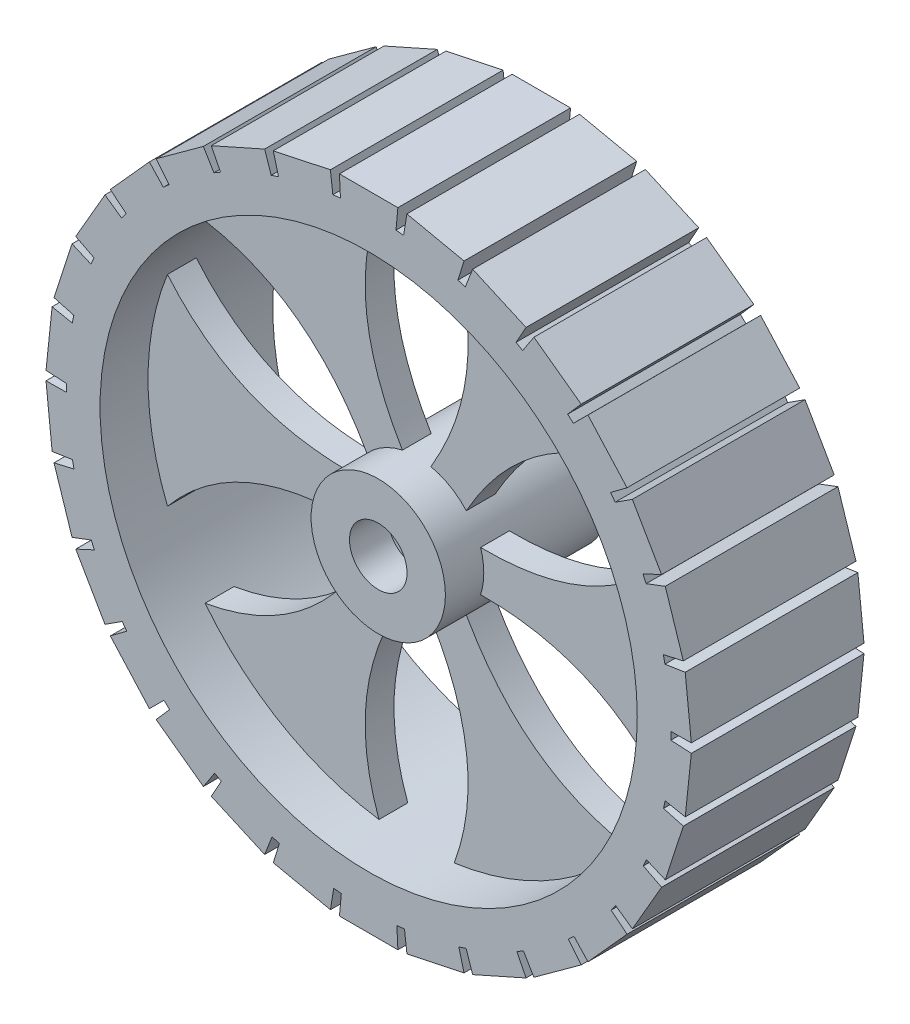
SolidWorks part; units mm, degrees
ref_plane "Front Plane" through (0, 0, 0) normal (0, 0, 1) x (1, 0, 0)
ref_plane "Top Plane" through (0, 0, 0) normal (0, 1, 0) x (1, 0, 0)
ref_plane "Right Plane" through (0, 0, 0) normal (1, 0, 0) x (0, 0, -1)
sketch "Sketch1" plane through (0, 0, 0) normal (0, 0, 1) x (1, 0, 0)
  line L0 (0, 31.5) -> (0, 33.5) construction
  line L1 (-4, 33.5) -> (4, 33.5)
  line L2 (-4, 33.5) -> (-3.7347, 31.2778)
  line L3 (4, 33.5) -> (3.6431, 31.2886)
  line L4 (3.0525, 33.5996) -> (2.85, 31.3708)
  line L5 (10.8776, 31.9363) -> (10.0688, 29.8474)
  line L6 (3.0525, 33.5996) -> (10.8776, 31.9363)
  line L7 (9.9715, 32.2307) -> (9.3101, 30.0927)
  line L8 (17.2799, 28.9768) -> (16.0544, 27.1018)
  line L9 (9.9715, 32.2307) -> (17.2799, 28.9768)
  line L10 (16.4547, 29.4532) -> (15.3632, 27.4995)
  line L11 (22.9269, 24.7509) -> (21.3383, 23.1717)
  line L12 (16.4547, 29.4532) -> (22.9269, 24.7509)
  line L13 (22.2188, 25.3885) -> (20.745, 23.7043)
  line L14 (27.5719, 19.4433) -> (25.6897, 18.2288)
  line L15 (22.2188, 25.3885) -> (27.5719, 19.4433)
  line L16 (27.0119, 20.2141) -> (25.2201, 18.8732)
  line L17 (31.0119, 13.2859) -> (28.9183, 12.4893)
  line L18 (27.0119, 20.2141) -> (31.0119, 13.2859)
  line L19 (30.6243, 14.1563) -> (28.5929, 13.2173)
  line L20 (33.0965, 6.5478) -> (30.883, 6.2039)
  line L21 (30.6243, 14.1563) -> (33.0965, 6.5478)
  line L22 (32.8984, 7.4798) -> (30.7161, 6.9836)
  line L23 (33.7346, -0.4764) -> (31.498, -0.3526)
  line L24 (32.8984, 7.4798) -> (33.7346, -0.4764)
  line L25 (33.7346, 0.4764) -> (31.4969, 0.4448)
  line L26 (32.8984, -7.4798) -> (30.7364, -6.8937)
  line L27 (33.7346, 0.4764) -> (32.8984, -7.4798)
  line L28 (33.0965, -6.5478) -> (30.9011, -6.1135)
  line L29 (30.6243, -14.1563) -> (28.6315, -13.1335)
  line L30 (33.0965, -6.5478) -> (30.6243, -14.1563)
  line L31 (31.0119, -13.2859) -> (28.9547, -12.4046)
  line L32 (27.0119, -20.2141) -> (25.2752, -18.7993)
  line L33 (31.0119, -13.2859) -> (27.0119, -20.2141)
  line L34 (27.5719, -19.4433) -> (25.7429, -18.1536)
  line L35 (22.2188, -25.3885) -> (20.8143, -23.6435)
  line L36 (27.5719, -19.4433) -> (22.2188, -25.3885)
  line L37 (22.9269, -24.7509) -> (21.4061, -23.1091)
  line L38 (16.4547, -29.4532) -> (15.4437, -27.4544)
  line L39 (22.9269, -24.7509) -> (16.4547, -29.4532)
  line L40 (17.2799, -28.9768) -> (16.1336, -27.0547)
  line L41 (9.9715, -32.2307) -> (9.3981, -30.0654)
  line L42 (17.2799, -28.9768) -> (9.9715, -32.2307)
  line L43 (10.8776, -31.9363) -> (10.1561, -29.8178)
  line L44 (3.0525, -33.5996) -> (2.9418, -31.3623)
  line L45 (10.8776, -31.9363) -> (3.0525, -33.5996)
  line L46 (4, -33.5) -> (3.7347, -31.2778)
  line L47 (-4, -33.5) -> (-3.6431, -31.2886)
  line L48 (4, -33.5) -> (-4, -33.5)
  line L49 (-3.0525, -33.5996) -> (-2.85, -31.3708)
  line L50 (-10.8776, -31.9363) -> (-10.0688, -29.8474)
  line L51 (-3.0525, -33.5996) -> (-10.8776, -31.9363)
  line L52 (-9.9715, -32.2307) -> (-9.3101, -30.0927)
  line L53 (-17.2799, -28.9768) -> (-16.0544, -27.1018)
  line L54 (-9.9715, -32.2307) -> (-17.2799, -28.9768)
  line L55 (-16.4547, -29.4532) -> (-15.3632, -27.4995)
  line L56 (-22.9269, -24.7509) -> (-21.3383, -23.1717)
  line L57 (-16.4547, -29.4532) -> (-22.9269, -24.7509)
  line L58 (-22.2188, -25.3885) -> (-20.745, -23.7043)
  line L59 (-27.5719, -19.4433) -> (-25.6897, -18.2288)
  line L60 (-22.2188, -25.3885) -> (-27.5719, -19.4433)
  line L61 (-27.0119, -20.2141) -> (-25.2201, -18.8732)
  line L62 (-31.0119, -13.2859) -> (-28.9183, -12.4893)
  line L63 (-27.0119, -20.2141) -> (-31.0119, -13.2859)
  line L64 (-30.6243, -14.1563) -> (-28.5929, -13.2173)
  line L65 (-33.0965, -6.5478) -> (-30.883, -6.2039)
  line L66 (-30.6243, -14.1563) -> (-33.0965, -6.5478)
  line L67 (-32.8984, -7.4798) -> (-30.7161, -6.9836)
  line L68 (-33.7346, 0.4764) -> (-31.498, 0.3526)
  line L69 (-32.8984, -7.4798) -> (-33.7346, 0.4764)
  line L70 (-33.7346, -0.4764) -> (-31.4969, -0.4448)
  line L71 (-32.8984, 7.4798) -> (-30.7364, 6.8937)
  line L72 (-33.7346, -0.4764) -> (-32.8984, 7.4798)
  line L73 (-33.0965, 6.5478) -> (-30.9011, 6.1135)
  line L74 (-30.6243, 14.1563) -> (-28.6315, 13.1335)
  line L75 (-33.0965, 6.5478) -> (-30.6243, 14.1563)
  line L76 (-31.0119, 13.2859) -> (-28.9547, 12.4046)
  line L77 (-27.0119, 20.2141) -> (-25.2752, 18.7993)
  line L78 (-31.0119, 13.2859) -> (-27.0119, 20.2141)
  line L79 (-27.5719, 19.4433) -> (-25.7429, 18.1536)
  line L80 (-22.2188, 25.3885) -> (-20.8143, 23.6435)
  line L81 (-27.5719, 19.4433) -> (-22.2188, 25.3885)
  line L82 (-22.9269, 24.7509) -> (-21.4061, 23.1091)
  line L83 (-16.4547, 29.4532) -> (-15.4437, 27.4544)
  line L84 (-22.9269, 24.7509) -> (-16.4547, 29.4532)
  line L85 (-17.2799, 28.9768) -> (-16.1336, 27.0547)
  line L86 (-9.9715, 32.2307) -> (-9.3981, 30.0654)
  line L87 (-17.2799, 28.9768) -> (-9.9715, 32.2307)
  line L88 (-10.8776, 31.9363) -> (-10.1561, 29.8178)
  line L89 (-3.0525, 33.5996) -> (-2.9418, 31.3623)
  line L90 (-10.8776, 31.9363) -> (-3.0525, 33.5996)
  circle A0 centre (0, 0) radius 3
  circle A1 centre (0, 0) radius 7
  circle A2 centre (0, 0) radius 28
  circle A3 centre (0, 0) radius 31.5
  point P131 (0, 0)
  dimension "D1" = 30
extrude "Boss-Extrude1" add sketch "Sketch1" along normal blind 18 contours A3 A2 region at (-3.2441, 30.4367, 0)
extrude "Boss-Extrude2" add sketch "Sketch1<5>" along normal blind 18 contours A3 L2 L90 L86 | A3 L88 L87 L83 | A3 L85 L84 L80 | A3 L82 L81 L77 | A3 L79 L78 L74 | A3 L76 L75 L71 | A3 L73 L72 L68 | A3 L70 L69 L65 | A3 L67 L66 L62 | A3 L64 L63 L59 | A3 L61 L60 L56 | A3 L58 L57 L53 | A3 L55 L54 L50 | A3 L52 L51 L47 | A3 L49 L48 L44 | A3 L46 L45 L41 | A3 L43 L42 L38 | A3 L40 L39 L35 | A3 L37 L36 L32 | A3 L34 L33 L29 | A3 L31 L30 L26 | A3 L28 L27 L23 | A3 L25 L24 L20 | A3 L22 L21 L17 | A3 L19 L18 L14 | A3 L16 L15 L11 | A3 L13 L12 L8 | A3 L10 L9 L5 | A3 L7 L6 L3 | A3 L0 L1 L89 | L0 A3 L4 L1 region at (-1.5148, 32.4824, 0) region at (1.4904, 32.4888, 0) region at (6.7297, 31.7809, 0) region at (-6.7785, 31.7705, 0) region at (13.1903, 29.6872, 0) region at (-13.2359, 29.6669, 0) region at (19.0743, 26.296, 0) region at (-19.1147, 26.2667, 0) region at (24.1248, 21.7556, 0) region at (-24.1582, 21.7185, 0) region at (28.1208, 16.2644, 0) region at (-28.1458, 16.2212, 0) region at (30.8879, 10.0623, 0) region at (-30.9033, 10.0149, 0) region at (32.305, 3.4205, 0) region at (-32.3102, 3.3708, 0) region at (-32.305, -3.4205, 0) region at (32.3102, -3.3708, 0) region at (-30.8879, -10.0623, 0) region at (30.9033, -10.0149, 0) region at (-28.1208, -16.2644, 0) region at (28.1458, -16.2212, 0) region at (-24.1248, -21.7556, 0) region at (24.1582, -21.7185, 0) region at (-19.0743, -26.296, 0) region at (19.1147, -26.2667, 0) region at (-13.1903, -29.6872, 0) region at (13.2359, -29.6669, 0) region at (-6.7297, -31.7809, 0) region at (6.7785, -31.7705, 0) region at (0.025, -32.4856, 0)
sketch "Sketch1<5>" plane through (0, 0, 0) normal (0, 0, 1) x (1, 0, 0) same geometry as "Sketch1"
ref_plane "Plane1" through (0, 0, 10) normal (0, 0, 1) x (1, 0, 0)
sketch "Sketch2" plane through (0, 0, 10) normal (0, 0, 1) x (1, 0, 0)
  circle A0 centre (0, 0) radius 28
extrude "Boss-Extrude4" add sketch "Sketch2" along normal blind 3
sketch "Sketch3" plane through (0, 0, 10) normal (0, 0, 1) x (1, 0, 0)
  circle A0 centre (0, 0) radius 3
  circle A1 centre (0, 0) radius 7
extrude "Boss-Extrude6" add sketch "Sketch3" along normal blind 7 and the other way blind 10
sketch "Sketch6" plane through (0, 0, 13) normal (0, 0, 1) x (1, 0, 0)
  circle A0 centre (0, 0) radius 0.625
extrude "Cut-Extrude5" cut sketch "Sketch6" against normal through all both and the other way through all
hole_wizard "Ø3.0mm Dowel Hole1" positions "3DSketch3" profile "Sketch10" hole size "Ø3.0" standard "ISO"
sketch3d "3DSketch3"
  point P0 (-6.9976, -0.1814, 5.5305)
sketch "Sketch10" plane through (-6.9976, -0.1814, 5.5305) normal (0, 0, 1) x (0.0259, -0.9997, 0)
  line L0 (0, 0) -> (0, 4.9013)
  line L1 (0, 4.9013) -> (1.5, 4)
  line L2 (1.5, 4) -> (1.5, 0)
  line L5 (1.5, 0) -> (0, 0)
  line L10 (0, 4.9013) -> (-1.5, 4) construction
  line L11 (0, -6.35) -> (0, 107.95) construction
  dimension "Hole Dia." = 3
  dimension "Hole Depth" = 4
  dimension "Drill Angle" = 118
sketch "Sketch12" plane through (0, 0, 10) normal (0, 0, 1) x (1, 0, 0)
  line L0 (0, 28) -> (0, -28) construction
  circle A0 centre (0, 0) radius 7
  circle A1 centre (0, 0) radius 28
  spline S0 degree 2 poles (-1.4848, 6.8407) (-7.7297, 17.3515) (-3.9237, 27.7237) knots 0 0 0 1 1 1
  spline S1 degree 2 poles (1.4848, 6.8407) (7.7297, 17.3515) (3.9237, 27.7237) knots 0 0 0 1 1 1
  spline S2 degree 2 poles (5.1818, 4.7062) (11.162, 15.3699) (22.0476, 17.2598) knots 0 0 0 1 1 1
  spline S3 degree 2 poles (6.6666, 2.1345) (18.8917, 1.9816) (25.9713, 10.4639) knots 0 0 0 1 1 1
  spline S4 degree 2 poles (6.6666, -2.1345) (18.8917, -1.9816) (25.9713, -10.4639) knots 0 0 0 1 1 1
  spline S5 degree 2 poles (5.1818, -4.7062) (11.162, -15.3699) (22.0476, -17.2598) knots 0 0 0 1 1 1
  spline S6 degree 2 poles (1.4848, -6.8407) (7.7297, -17.3515) (3.9237, -27.7237) knots 0 0 0 1 1 1
  spline S7 degree 2 poles (-1.4848, -6.8407) (-7.7297, -17.3515) (-3.9237, -27.7237) knots 0 0 0 1 1 1
  spline S8 degree 2 poles (-5.1818, -4.7062) (-11.162, -15.3699) (-22.0476, -17.2598) knots 0 0 0 1 1 1
  spline S9 degree 2 poles (-6.6666, -2.1345) (-18.8917, -1.9816) (-25.9713, -10.4639) knots 0 0 0 1 1 1
  spline S10 degree 2 poles (-6.6666, 2.1345) (-18.8917, 1.9816) (-25.9713, 10.4639) knots 0 0 0 1 1 1
  spline S11 degree 2 poles (-5.1818, 4.7062) (-11.162, 15.3699) (-22.0476, 17.2598) knots 0 0 0 1 1 1
  point P9 (0, 0)
  point P45 (0, 0)
extrude "Cut-Extrude7" cut sketch "Sketch12" against normal through all both and the other way through all contours L0 A1 S0 A0 | A1 L0 A0 S1 | A0 S11 A1 S10 | A0 S9 A1 S8 | L0 A0 S7 A1 | A0 L0 A1 S6 | A0 S5 A1 S4 | A0 S3 A1 S2 region at (2.3059, 18.3521, 10) region at (-2.3059, 18.3521, 10) region at (2.3059, -18.3521, 10) region at (-2.3059, -18.3521, 10) region at (15.8934, 9.176, 10) region at (-15.8934, 9.176, 10) region at (-15.8934, -9.176, 10) region at (15.8934, -9.176, 10)
sketch "Sketch11" plane through (0, 0, 10) normal (0, 0, -1) x (-1, 0, 0)
scale "Scale1" scale about centroid uniform scaling yes scale factor 0.5
scale "Scale2" scale about centroid uniform scaling yes scale factor 1.25
scale "Scale3" scale about centroid uniform scaling yes scale factor 1.25
scale "Scale4" scale about centroid uniform scaling yes scale factor 1.1
scale "Scale5" scale about centroid uniform scaling yes scale factor 0.8
scale "Scale6" scale about centroid uniform scaling yes scale factor 1.1
